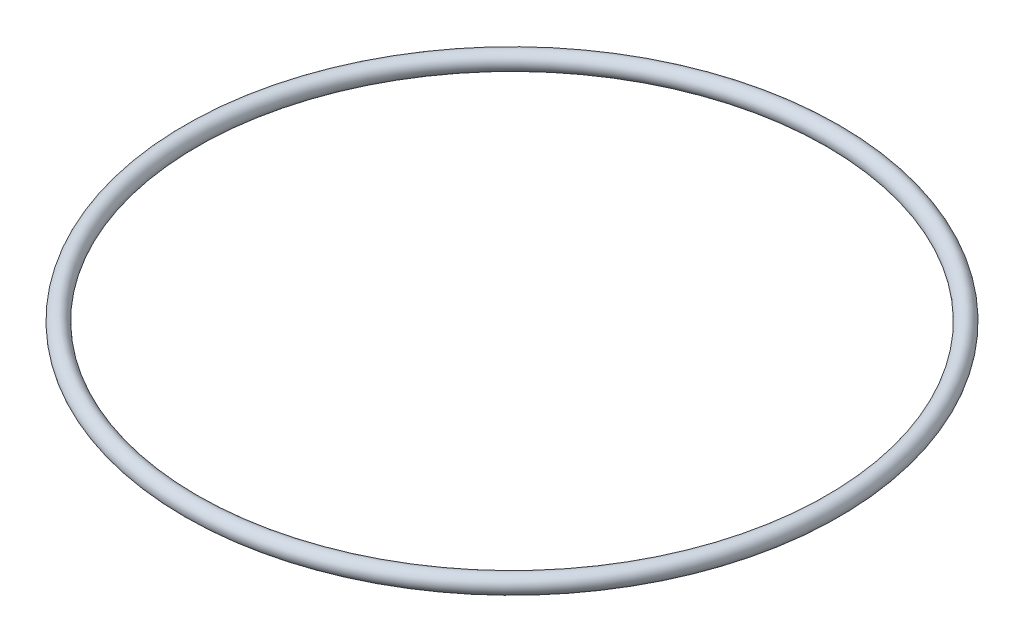
SolidWorks part; units mm, degrees
ref_plane "Front Plane" through (0, 0, 0) normal (0, 0, 1) x (1, 0, 0)
ref_plane "Top Plane" through (0, 0, 0) normal (0, 1, 0) x (1, 0, 0)
ref_plane "Right Plane" through (0, 0, 0) normal (1, 0, 0) x (0, 0, -1)
sketch "Sketch1" plane through (0, 0, 0) normal (1, 0, 0) x (0, 0, -1)
  line L0 (0, 0) -> (-55, 0) construction
  line L1 (0, 0) -> (0, 30.901) construction
  circle A0 centre (-55, 0) radius 1.5
  dimension "D1" = 3
  dimension "D2" = 55
revolve "Revolve1" add sketch "Sketch1" angle 360 about L1
ref_axis "Axis1" through (0, 32.521, 0) along (0, -1, 0)
